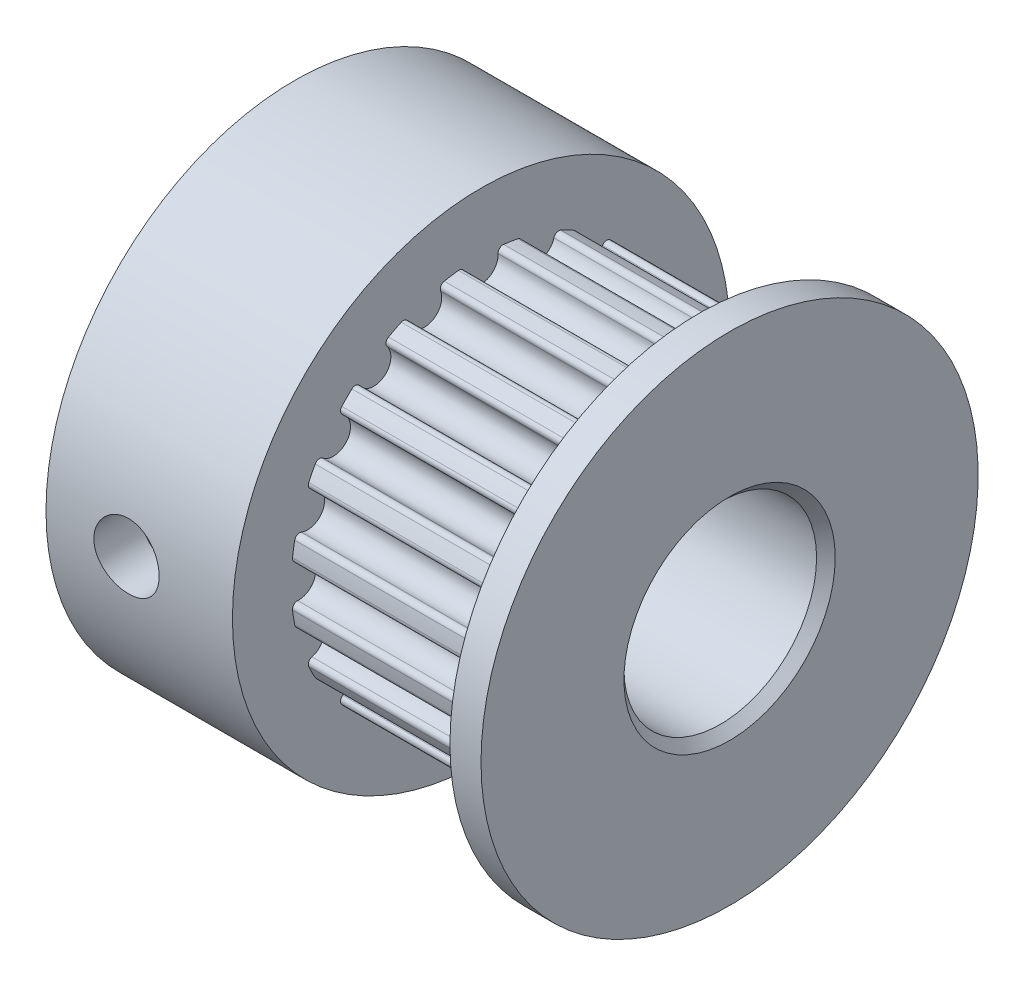
SolidWorks part; units mm, degrees
note: '?' marks a value the reader was unsure of.
other "Main_Body" parameters "D16"=0.5
material "6061-O (SS)"
ref_plane "Сверху" through (0, 0, 0) normal (0, 0, 1) x (1, 0, 0)
ref_plane "Справа" through (0, 0, 0) normal (0, 1, 0) x (1, 0, 0)
ref_plane "Спереди" through (0, 0, 0) normal (1, 0, 0) x (0, 0, -1)
sketch "Эскиз1" plane through (0, 0, 0) normal (0, 0, 1) x (1, 0, 0)
  line L0 (0, 0) -> (0, 7.2132)
  line L1 (0, 7.2132) -> (0, 8)
  line L2 (0, 8) -> (6, 8)
  line L3 (6, 8) -> (6, 7.2132)
  line L4 (6, 6.11) -> (13, 6.11)
  line L5 (13, 6.11) -> (13, 7.2132)
  line L6 (13, 8) -> (14, 8)
  line L7 (14, 0) -> (14, 8)
  line L11 (0, 0) -> (14, 0)
  line L12 (6, 7.2132) -> (6, 6.11)
  line L13 (13, 7.2132) -> (13, 8)
  point P8 (0, 0)
  point P10 (14.45, 8)
  point P11 (0, 0)
  point P12 (0, 0)
  point P16 (0, 0)
  point P17 (0, 0)
  dimension "D6" = 6.11
  dimension "D7" = 6
  dimension "D8" = 7
  dimension "D10" = 14
  dimension "D11" = 8
revolve "Body" add sketch "Эскиз1" angle 360 about L11
sketch "Эскиз2" plane through (14, 0, 0) normal (1, 0, 0) x (0, 0, -1)
  circle A0 centre (0, 0) radius 3.1
  dimension "D1" = 6.2
extrude "Bore" cut sketch "Эскиз2" against normal through all
sketch "Эскиз3" plane through (6, 0, 0) normal (1, 0, 0) x (0, 0, -1)
  line L0 (0, 0) -> (9.7637, 0) construction
  circle A0 centre (5.5827, -1.8139) radius 0.55
  circle A1 centre (0, 0) radius 6.42 construction
  circle A2 centre (4.7489, -3.4503) radius 0.55
  circle A3 centre (3.4503, -4.7489) radius 0.55
  circle A4 centre (1.8139, -5.5827) radius 0.55
  circle A5 centre (0, -5.87) radius 0.55
  circle A6 centre (5.87, 0) radius 0.55
  circle A7 centre (-1.8139, -5.5827) radius 0.55
  circle A8 centre (-3.4503, -4.7489) radius 0.55
  circle A9 centre (-4.7489, -3.4503) radius 0.55
  circle A10 centre (-5.5827, -1.8139) radius 0.55
  circle A11 centre (-5.87, 0) radius 0.55
  circle A12 centre (-5.5827, 1.8139) radius 0.55
  circle A13 centre (-4.7489, 3.4503) radius 0.55
  circle A14 centre (-3.4503, 4.7489) radius 0.55
  circle A17 centre (-1.8139, 5.5827) radius 0.55
  circle A18 centre (0, 5.87) radius 0.55
  circle A19 centre (1.8139, 5.5827) radius 0.55
  circle A20 centre (3.4503, 4.7489) radius 0.55
  circle A21 centre (4.7489, 3.4503) radius 0.55
  circle A22 centre (5.5827, 1.8139) radius 0.55
  point P45 (0, 0)
  dimension "D1" = 12.84
  dimension "D2" = 20
  dimension "D3" = 1.1
extrude "20T" cut sketch "Эскиз3" along normal blind 7
fillet "Fillet" radius 0.16 40 edges at (9.5, 0.5045, -6.0891) (9.5, -0.5045, -6.0891) (9.5, -1.4019, -5.947) (9.5, -2.3614, -5.6352) (9.5, -3.171, -5.2227) (9.5, -3.9872, -4.6297) (9.5, -4.6297, -3.9872) (9.5, -5.2227, -3.171) (9.5, -5.6352, -2.3614) (9.5, -5.947, -1.4019) (9.5, -6.0891, -0.5045) (9.5, -6.0891, 0.5045) (9.5, -5.947, 1.4019) (9.5, -5.6352, 2.3614) (9.5, -5.2227, 3.171) (9.5, -4.6297, 3.9872) (9.5, -3.9872, 4.6297) (9.5, -3.171, 5.2227) (9.5, -2.3614, 5.6352) (9.5, -1.4019, 5.947) (9.5, -0.5045, 6.0891) (9.5, 0.5045, 6.0891) (9.5, 1.4019, 5.947) (9.5, 2.3614, 5.6352) (9.5, 3.171, 5.2227) (9.5, 3.9872, 4.6297) (9.5, 4.6297, 3.9872) (9.5, 5.2227, 3.171) (9.5, 5.6352, 2.3614) (9.5, 5.947, 1.4019) (9.5, 6.0891, 0.5045) (9.5, 6.0891, -0.5045) (9.5, 5.947, -1.4019) (9.5, 5.6352, -2.3614) (9.5, 5.2227, -3.171) (9.5, 4.6297, -3.9872) (9.5, 3.9872, -4.6297) (9.5, 3.171, -5.2227) (9.5, 2.3614, -5.6352) (9.5, 1.4019, -5.947)
ref_axis "Axis1" through (0, 0, 0) along (1, 0, 0)?
chamfer "Chamfer2" distance 0.3 angle 45 2 edges at (14, 0, -3.1) (0, 0, -3.1)
sketch "Sketch1" plane through (0, 0, 0) normal (-1, 0, 0) x (0, 0, 1)
  line L1 (6.5, 2.05) -> (4.8, 2.05)
  line L2 (6.5, 2.05) -> (6.5, -2.05)
  line L3 (6.5, -2.05) -> (4.8, -2.05)
  line L4 (4.8, 2.05) -> (4.8, -2.05)
  line L5 (2.05, -4.8) -> (-2.05, -4.8)
  line L6 (2.05, -4.8) -> (2.05, -6.5)
  line L7 (2.05, -6.5) -> (-2.05, -6.5)
  line L8 (-2.05, -4.8) -> (-2.05, -6.5)
  circle A2 centre (0, 0) radius 8 construction
  point P4 (8, 0)
  point P5 (0, -8)
  point P6 (8, 0)
  point P8 (0, -6.5)
  point P9 (6.5, 0)
  point P14 (0, 0)
  point P15 (0, -8)
  point P17 (0, -7.2132)
  point P18 (0, -7.2132)
  point P20 (0, 0)
  dimension "D1" = 4.1
  dimension "D2" = 1.5
  dimension "D3" = 1.7
  dimension "D4" = 1.5
extrude "Cut-Extrude1" cut sketch "Sketch1" against normal offset from surface (5 mm away) 1
sketch "Sketch2" plane through (0, 0, 4.8) normal (0, 0, 1) x (1, 0, 0)
  line L0 (5, -2.05) -> (5, 2.05) construction
  line L1 (4.9, 0) -> (3.7453, 2)
  line L2 (3.7453, 2) -> (1.4359, 2)
  line L3 (1.4359, 2) -> (0.2812, 0)
  line L4 (0.2812, 0) -> (1.4359, -2)
  line L5 (1.4359, -2) -> (3.7453, -2)
  line L6 (3.7453, -2) -> (4.9, 0)
  line L7 (5, -2.05) -> (0, -2.05) construction
  circle A0 centre (2.5906, 0) radius 2 construction
  circle A1 centre (2.5906, 0) radius 1.05
  point P11 (0, 0)
  dimension "D2" = 2.1
  dimension "D1" = 0.1
  dimension "D3" = 0.05
extrude "Cut-Extrude2" cut sketch "Sketch2" against normal up to next and the other way through all contours A1
sketch "Sketch3" plane through (0, -4.8, 0) normal (0, -1, 0) x (1, 0, 0)
  line L0 (5, -2.05) -> (5, 2.05) construction
  line L1 (4.9, 0) -> (3.7453, 2)
  line L2 (3.7453, 2) -> (1.4359, 2)
  line L3 (1.4359, 2) -> (0.2812, 0)
  line L4 (0.2812, 0) -> (1.4359, -2)
  line L5 (1.4359, -2) -> (3.7453, -2)
  line L6 (3.7453, -2) -> (4.9, 0)
  line L7 (5, 2.05) -> (0, 2.05) construction
  circle A0 centre (2.5906, 0) radius 2 construction
  circle A1 centre (2.5906, 0) radius 1.05
  dimension "D1" = 4
  dimension "D4" = 2.1
  dimension "D2" = 0.1
  dimension "D3" = 0.05
extrude "Cut-Extrude3" cut sketch "Sketch3" against normal up to next and the other way through all contours A1
